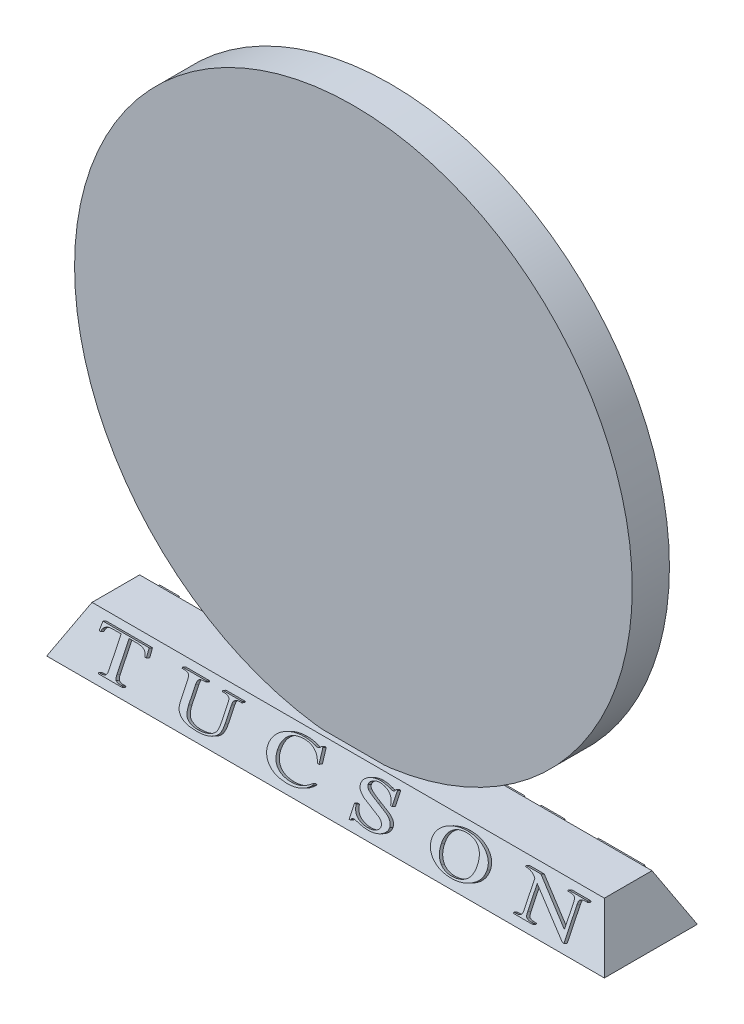
SolidWorks part; units mm, degrees
ref_plane "Front Plane" through (0, 0, 0) normal (0, 0, 1) x (1, 0, 0)
ref_plane "Top Plane" through (0, 0, 0) normal (0, 1, 0) x (1, 0, 0)
ref_plane "Right Plane" through (0, 0, 0) normal (1, 0, 0) x (0, 0, -1)
sketch "Sketch1" plane through (0, 0, 0) normal (0, 1, 0) x (1, 0, 0)
  line L1 (38.1, 6.35) -> (-38.1, 6.35)
  line L2 (38.1, 6.35) -> (38.1, -6.35)
  line L3 (38.1, -6.35) -> (-38.1, -6.35)
  line L4 (-38.1, 6.35) -> (-38.1, -6.35)
  line L5 (38.1, 6.35) -> (-38.1, -6.35) construction
  line L6 (38.1, -6.35) -> (-38.1, 6.35) construction
  point P0 (0, 0)
  dimension "D1" = 76.2
  dimension "D2" = 12.7
extrude "Boss-Extrude1" add sketch "Sketch1" along normal blind 6.35 draft 26
sketch "Sketch2" plane through (0, 0, 0) normal (0, 0, 1) x (1, 0, 0)
  circle A0 centre (0, 44.196) radius 38.1
  dimension "D1" = 76.2
extrude "Boss-Extrude2" add sketch "Sketch2" along normal blind 2.54 and the other way blind 2.54 separate body
sketch "Sketch3" plane through (0, 2.5019, -5.1297) normal (0, 0.4384, -0.8988) x (-1, 0, 0)
  text T0 "TUCSON" font "Times New Roman" height in points 20
extrude "Boss-Extrude3" add sketch "Sketch3" along normal blind 0.508 separate body
sketch "Sketch8" plane through (0, 2.5019, 5.1297) normal (0, 0.4384, 0.8988) x (1, 0, 0)
  text T0 "TUCSON" font "Times New Roman" height in points 20
extrude "Boss-Extrude4" add sketch "Sketch8" along normal blind 0.508
